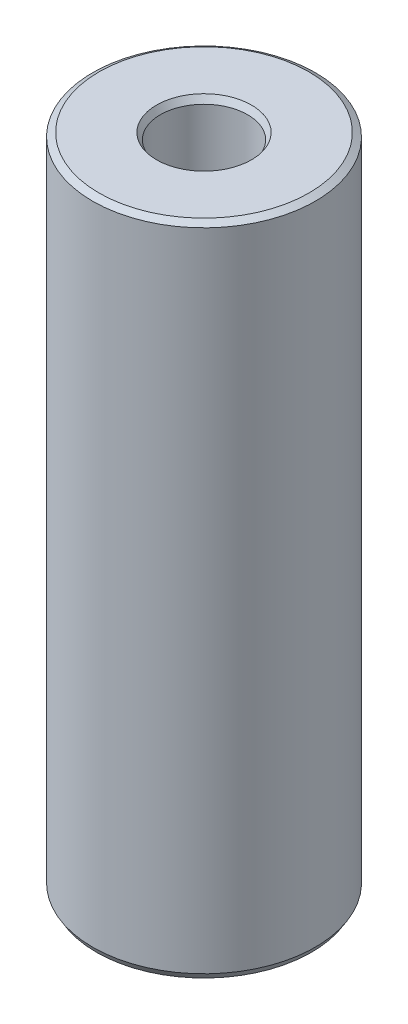
SolidWorks part; units mm, degrees
ref_plane "Front Plane" through (0, 0, 0) normal (0, 0, 1) x (1, 0, 0)
ref_plane "Top Plane" through (0, 0, 0) normal (0, 1, 0) x (1, 0, 0)
ref_plane "Right Plane" through (0, 0, 0) normal (1, 0, 0) x (0, 0, -1)
sketch "Sketch1" plane through (0, 0, 0) normal (0, 1, 0) x (1, 0, 0)
  circle A0 centre (0, 0) radius 35
  dimension "SLEEVE_OD" = 70
extrude "Boss-Extrude1" add sketch "Sketch1" along normal blind 206.2461
sketch "Sketch2" plane through (0, 0, 0) normal (0, 1, 0) x (1, 0, 0)
  circle A0 centre (0, 0) radius 13.708
  dimension "BORE_D" = 27.416
extrude "Cut-Extrude1" cut sketch "Sketch2" along normal through all
chamfer "Chamfer1" distance 1.2149 angle 58.918 4 edges at (0, 206.2461, 13.708) (0, 0, 13.708) (0, 0, 35) (0, 206.2461, 35) first distance on face at (0, 206.2461, 13.708) first distance on face at (0, 0, 13.708) first distance on face at (0, 206.2461, 35)
